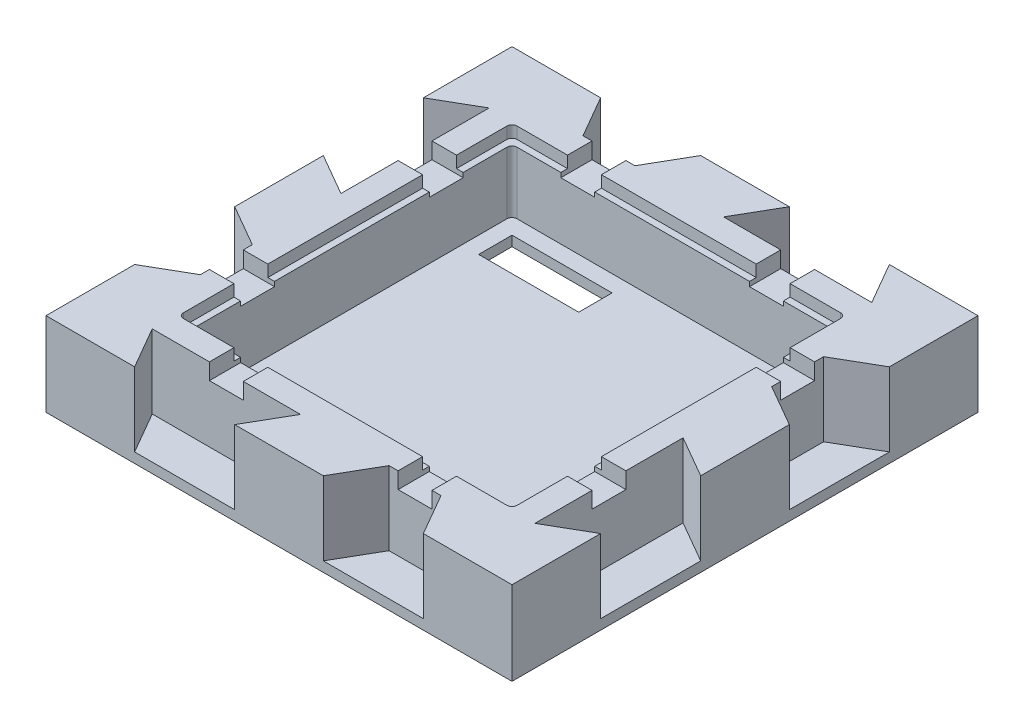
SolidWorks part; units mm, degrees
material "Macor"
ref_plane "Front Plane" through (0, 0, 0) normal (0, 0, 1) x (1, 0, 0)
ref_plane "Top Plane" through (0, 0, 0) normal (0, 1, 0) x (1, 0, 0)
ref_plane "Right Plane" through (0, 0, 0) normal (1, 0, 0) x (0, 0, -1)
sketch "Sketch1" plane through (0, 0, 0) normal (0, 1, 0) x (1, 0, 0)
  line L1 (-69.85, -69.85) -> (69.85, -69.85)
  line L2 (-69.85, -69.85) -> (-69.85, 69.85)
  line L3 (-69.85, 69.85) -> (69.85, 69.85)
  line L4 (69.85, -69.85) -> (69.85, 69.85)
  line L5 (-69.85, -69.85) -> (69.85, 69.85) construction
  line L6 (-69.85, 69.85) -> (69.85, -69.85) construction
  point P0 (0, 0)
  dimension "D1" = 139.7
extrude "Boss-Extrude1" add sketch "Sketch1" along normal mid plane 25.4
sketch "Sketch2" plane through (0, 12.7, 0) normal (0, 1, 0) x (1, 0, 0)
  line L0 (69.85, -69.85) -> (69.85, 69.85) construction
  line L1 (-69.85, -69.85) -> (69.85, -69.85)
  line L2 (-69.85, -69.85) -> (-69.85, 69.85)
  line L3 (-69.85, 69.85) -> (69.85, 69.85)
  line L4 (69.85, -69.85) -> (69.85, 69.85)
  line L5 (-69.85, -69.85) -> (69.85, 69.85) construction
  line L6 (-69.85, 69.85) -> (69.85, -69.85) construction
  point P0 (0, 0)
  dimension "D1" = 0
extrude "Cut-Extrude1" cut sketch "Sketch2" against normal offset from surface (0.3 mm away) 0.3 up to face at (0, 12.7, 0)
sketch "Sketch4" plane through (0, 12.4, 0) normal (0, 1, 0) x (1, 0, 0)
  line L0 (-43.2833, -69.85) -> (-50.5002, -57.35)
  line L2 (-50.5002, -57.35) -> (-6.0665, -57.35)
  line L3 (-6.0665, -57.35) -> (-13.2833, -69.85)
  line L4 (-13.2833, -69.85) -> (-43.2833, -69.85)
  line L5 (43.2833, -69.85) -> (36.0665, -57.35)
  line L24 (43.2833, -69.85) -> (13.2833, -69.85)
  line L25 (-69.85, -69.85) -> (-43.2833, -69.85) construction
  line L26 (-13.2833, -69.85) -> (13.2833, -69.85) construction
  line L27 (43.2833, -69.85) -> (69.85, -69.85) construction
  line L28 (36.0665, -57.35) -> (20.5002, -57.35)
  line L30 (13.2833, -69.85) -> (20.5002, -57.35)
  line L31 (-69.85, 69.85) -> (-69.85, -69.85) construction
  line L32 (69.85, -69.85) -> (69.85, 69.85) construction
  line L33 (-69.85, -69.85) -> (69.85, -69.85) construction
  dimension "D2" = 30
  dimension "D1" = 60
  dimension "D3" = 12.5
  dimension "D4" = 60
extrude "Cut-Extrude2" cut sketch "Sketch4" against normal offset from surface 3 and the other way through all up to face at (0, -12.7, 0)
sketch "Sketch18" plane through (0, 0, 57.35) normal (0, 0, 1) x (1, 0, 0)
  line L1 (0, -13.805) -> (0, 13.805) construction
  line L3 (23.2033, 12.4) -> (23.2033, 7.525)
  line L4 (23.2033, 7.525) -> (33.3633, 7.525)
  line L5 (33.3633, 12.4) -> (33.3633, 7.525)
  line L6 (-23.2033, 12.4) -> (-33.3633, 12.4)
  line L7 (-33.3633, 12.4) -> (-33.3633, 7.525)
  line L8 (-23.2033, 12.4) -> (-23.2033, 7.525)
  line L9 (-23.2033, 7.525) -> (-33.3633, 7.525)
  line L10 (23.2033, 12.4) -> (33.3633, 12.4)
  line L11 (20.5002, 12.4) -> (36.0665, 12.4) construction
  point P7 (28.2833, 12.4)
  point P14 (28.2833, 12.4)
  dimension "D1" = 10.16
  dimension "D2" = 4.875
extrude "Cut-Extrude6" cut sketch "Sketch18" against normal blind 20
ref_axis "Axis1" through (0, 29.6009, 0) along (0, -1, 0)
pattern_circular "CirPattern1" count 4 over 360 about axis through (0, 29.6009, 0) along (0, -1, 0) of "Cut-Extrude2", "Cut-Extrude6"
sketch "Sketch19" plane through (0, 12.4, 0) normal (0, 1, 0) x (1, 0, 0)
  line L1 (-50, -50) -> (50, -50)
  line L2 (-50, -50) -> (-50, 50)
  line L3 (-50, 50) -> (50, 50)
  line L4 (50, -50) -> (50, 50)
  line L5 (-50, -50) -> (50, 50) construction
  line L6 (-50, 50) -> (50, -50) construction
  point P0 (0, 0)
  dimension "D1" = 100
extrude "Cut-Extrude8" cut sketch "Sketch19" against normal blind 3.5
sketch "Sketch20" plane through (0, 8.9, 0) normal (0, 1, 0) x (1, 0, 0)
  line L1 (-48, -48) -> (48, -48)
  line L2 (-48, -48) -> (-48, 48)
  line L3 (-48, 48) -> (48, 48)
  line L4 (48, -48) -> (48, 48)
  line L5 (-48, -48) -> (48, 48) construction
  line L6 (-48, 48) -> (48, -48) construction
  point P0 (0, 0)
  dimension "D1" = 96
extrude "Cut-Extrude9" cut sketch "Sketch20" against normal blind 18.6
sketch "Sketch21" plane through (0, -9.7, 0) normal (0, 1, 0) x (1, 0, 0)
  line L0 (-48, 48) -> (-48, -48) construction
  line L1 (-13, 33) -> (-43, 33)
  line L2 (-13, 33) -> (-13, 43)
  line L3 (-13, 43) -> (-43, 43)
  line L4 (-43, 33) -> (-43, 43)
  line L5 (48, 48) -> (-48, 48) construction
  dimension "D1" = 30
  dimension "D2" = 10
  dimension "D3" = 5
  dimension "D4" = 5
extrude "Cut-Extrude10" cut sketch "Sketch21" against normal through all
fillet "Fillet2" radius 1.5 8 edges at (-50, 10.65, -50) (-50, 10.65, 50) (50, 10.65, 50) (50, 10.65, -50) (48, -0.4, 48) (-48, -0.4, 48) (-48, -0.4, -48) (48, -0.4, -48)
pattern_circular "CirPattern2" count 2 over 360 about axis through (0, 29.6009, 0) along (0, -1, 0) of "Cut-Extrude10"
equation "\"panel_width\"= 5.5in"
equation "\"finger_joint_width\"= 30mm"
equation "\"D1@Sketch1\"=\"panel_width\""
equation "\"D2@Sketch4\"=\"finger_joint_width\""
